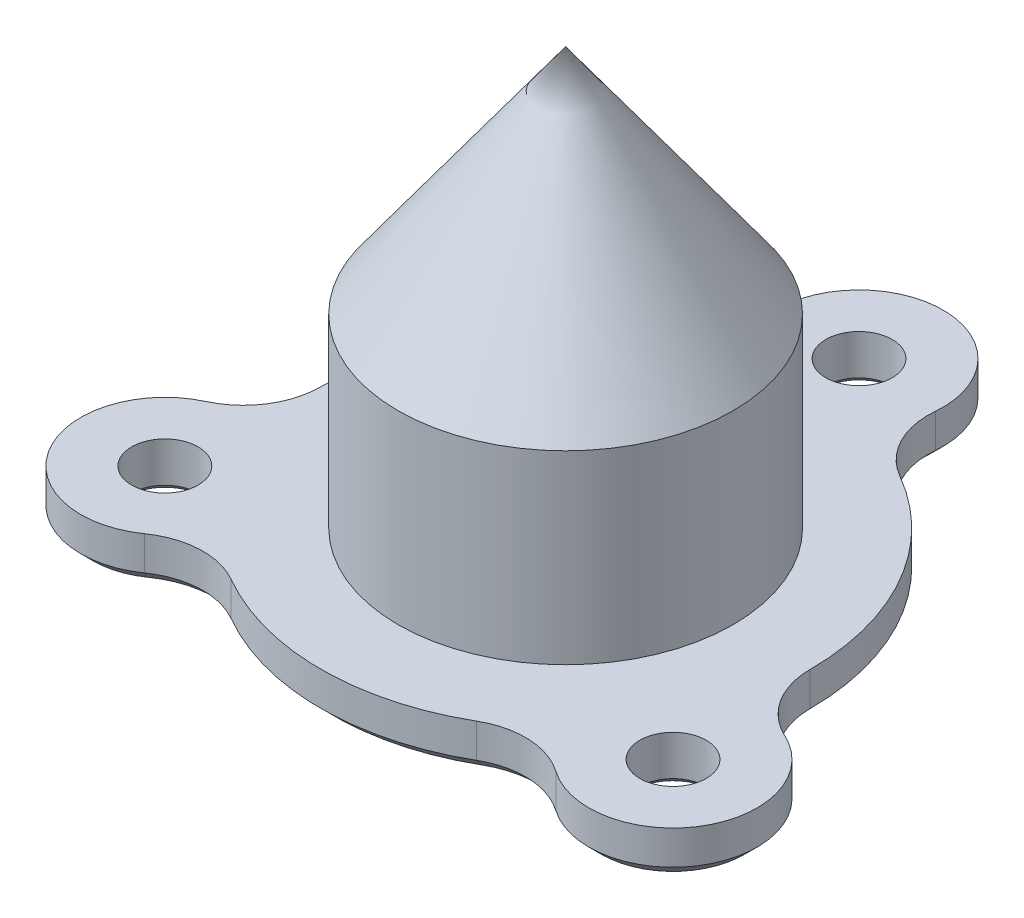
SolidWorks part; units mm, degrees
ref_plane "Front Plane" through (0, 0, 0) normal (0, 0, 1) x (1, 0, 0)
ref_plane "Top Plane" through (0, 0, 0) normal (0, 1, 0) x (1, 0, 0)
ref_plane "Right Plane" through (0, 0, 0) normal (1, 0, 0) x (0, 0, -1)
sketch "Sketch1" plane through (0, 0, 0) normal (0, 1, 0) x (1, 0, 0)
  line L0 (0, 0) -> (0, 32.0938) construction
  line L1 (0, 19) -> (7.7655, 19) construction
  circle A0 centre (0, 0) radius 10.85
  circle A1 centre (0, 19) radius 2.15
  arc A6 (5.4282, 18.5131) -> (-5.4282, 18.5131) centre (0, 19) ccw
  arc A7 (-7.9122, 13.7339) -> (-15.85, -0.0147) centre (0, 0) ccw
  arc A10 (5.4282, 18.5131) -> (7.9122, 13.7339) centre (10.4082, 18.0663) ccw
  arc A11 (-5.4282, 18.5131) -> (-7.9122, 13.7339) centre (-10.4082, 18.0663) cw
  circle A12 centre (0, 19) radius 5.45 construction
  arc A13 (13.3187, -13.9575) -> (18.7469, -4.5556) centre (16.4545, -9.5) ccw
  circle A14 centre (0, 0) radius 15.85 construction
  circle A15 centre (16.4545, -9.5) radius 2.15
  arc A16 (13.3187, -13.9575) -> (7.9378, -13.7191) centre (10.4418, -18.0469) ccw
  arc A17 (18.7469, -4.5556) -> (15.85, -0.0147) centre (20.85, -0.0194) cw
  arc A18 (-18.7469, -4.5556) -> (-13.3187, -13.9575) centre (-16.4545, -9.5) ccw
  circle A19 centre (-16.4545, -9.5) radius 2.15
  arc A20 (-18.7469, -4.5556) -> (-15.85, -0.0147) centre (-20.85, -0.0194) ccw
  arc A21 (-13.3187, -13.9575) -> (-7.9378, -13.7191) centre (-10.4418, -18.0469) cw
  arc A22 (15.85, -0.0147) -> (7.9122, 13.7339) centre (0, 0) ccw
  arc A23 (-7.9378, -13.7191) -> (7.9378, -13.7191) centre (0, 0) ccw
  point P13 (0, 0)
  point P15 (4.3, 19)
  point P17 (15, 0)
  point P41 (0, 0)
  dimension "D1" = 21.7
  dimension "D3" = 4.3
  dimension "D4" = 10
  dimension "D2" = 19
  dimension "D5" = 5
  dimension "D6" = 3.3
  dimension "D7" = 3
extrude "Boss-Extrude1" add sketch "Sketch1" along normal blind 3
extrude "Boss-Extrude2" add sketch "Sketch1<2>" along normal blind 15 contours A0 region at (0, 0, 0)
sketch "Sketch1<2>" plane through (0, 0, 0) normal (0, 1, 0) x (1, 0, 0) same geometry as "Sketch1"
sketch "Sketch2" plane through (0, 0, 0) normal (0, 0, 1) x (1, 0, 0)
  line L0 (0, 18.4135) -> (0, 7.4654) construction
  line L1 (0, 15) -> (10.85, 15)
  line L2 (10.85, 15) -> (-10.85, 15) construction
  line L3 (10.85, 15) -> (0, 30)
  line L4 (0, 30) -> (0, 15)
  dimension "D1" = 15
revolve "Revolve1" add sketch "Sketch2" angle 360 about L0
chamfer "Chamfer1" distance 0.8 angle 45 12 edges at (0, 0, -24.45) (-5.9717, 0, -15.7604) (5.9717, 0, -15.7604) (-13.7265, 0, -7.925) (13.7265, 0, -7.925) (-16.6347, 0, 2.7086) (16.6347, 0, 2.7086) (-21.1743, 0, 12.225) (21.1743, 0, 12.225) (-10.6631, 0, 13.0518) (10.6631, 0, 13.0518) (0, 0, 15.85)
chamfer "Chamfer2" distance 0.4 angle 45 3 edges at (-16.4545, 0, 11.65) (16.4545, 0, 11.65) (0, 0, -16.85)
